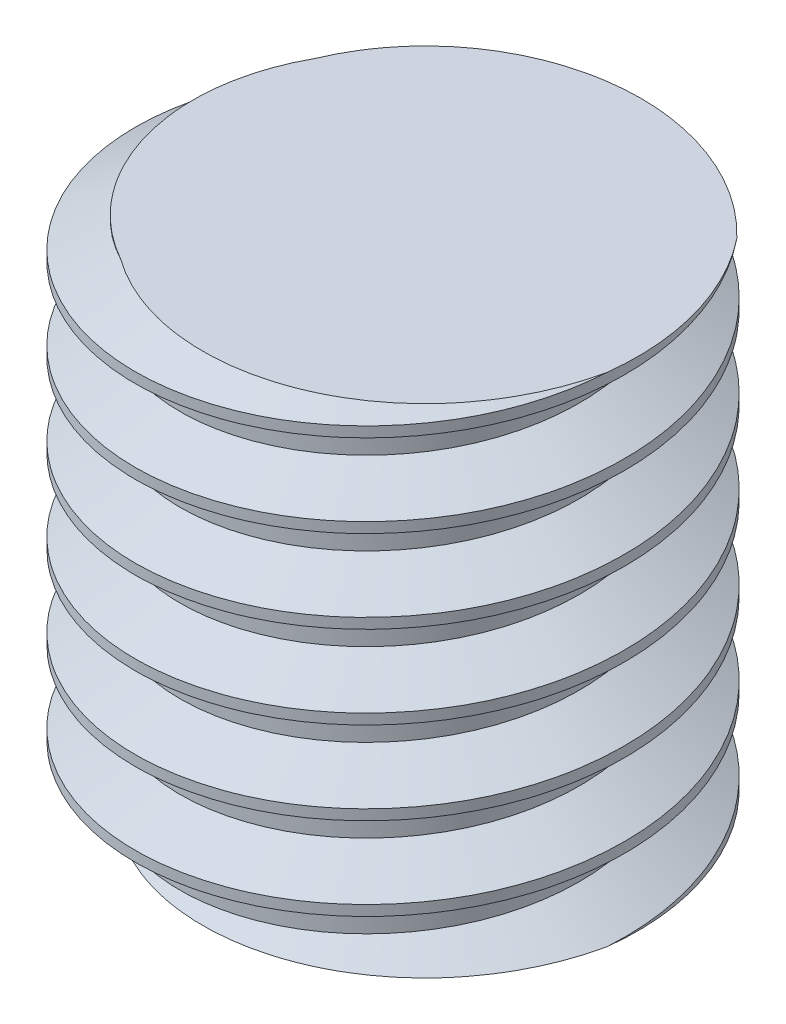
SolidWorks part; units mm, degrees
ref_plane "Front Plane" through (0, 0, 0) normal (0, 0, 1) x (1, 0, 0)
ref_plane "Top Plane" through (0, 0, 0) normal (0, 1, 0) x (1, 0, 0)
ref_plane "Right Plane" through (0, 0, 0) normal (1, 0, 0) x (0, 0, -1)
sketch "Sketch1" plane through (0, 0, 0) normal (0, 1, 0) x (1, 0, 0)
  circle A0 centre (0, 0) radius 7.5
  dimension "D1" = 15
extrude "Boss-Extrude1" add sketch "Sketch1" along normal blind 15.24
thread "Thread1" pitch 2.54 method cut profile "Thread Profile2" start angle 0, offset 3.54, length 0, pitch 2.54, diameter 15
ref_plane "Plane2" through (-7.5, 18.78, 0) normal (0, 0, 1) x (-1, 0, 0)
sketch "Thread Profile2" plane through (-7.5, 18.78, 0) normal (0, 0, 1) x (-1, 0, 0)
  line L0 (0, 0) -> (0, 2.54) construction
  line L11 (0, 0) -> (0, 2.2225)
  line L12 (0, 2.2225) -> (-1.3748, 1.4287)
  line L13 (-1.3748, 1.4287) -> (-1.3748, 0.7937)
  line L15 (-1.3748, 0.7937) -> (0, 0)
  line L17 (-1.3748, 1.1112) -> (0, 1.1112) construction
  point P2 (0, 0)
  dimension "Pitch" = 2.54
  dimension "Profile_Angle" = 60
  dimension "Profile_Land" = 0.635
  dimension "Profile_Height" = 1.3748
